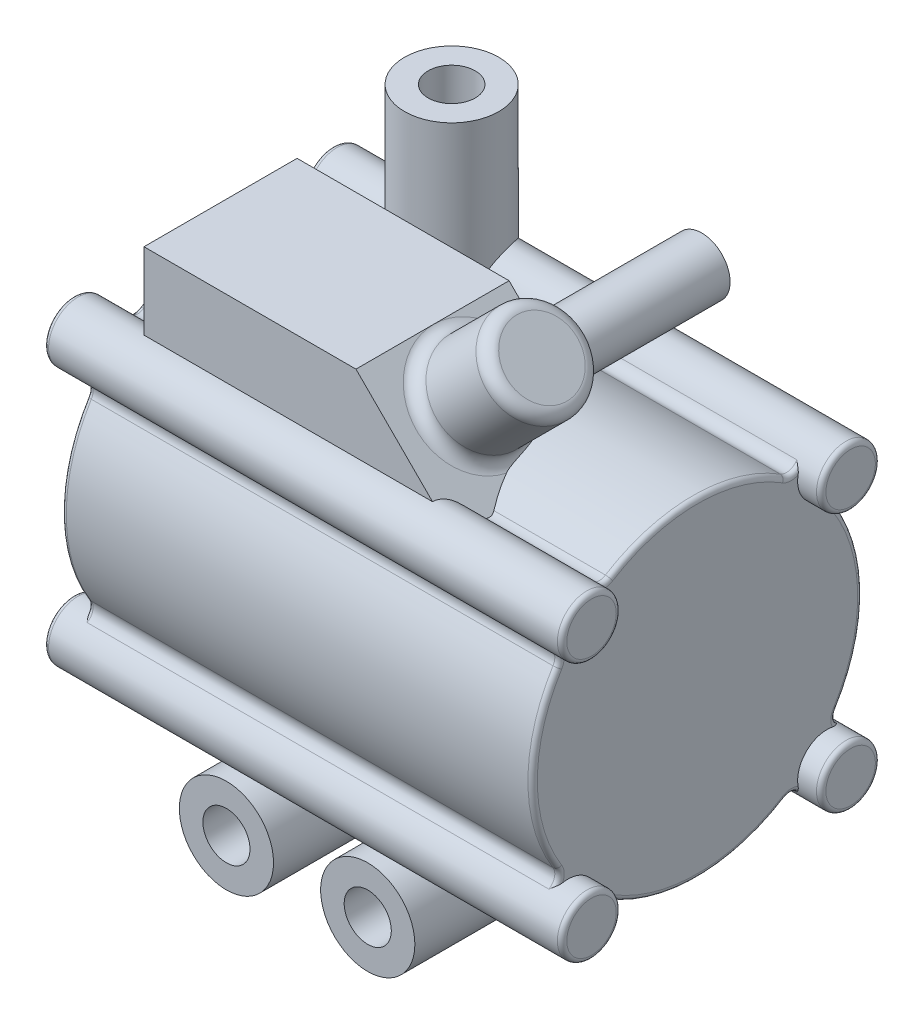
SolidWorks part; units mm, degrees
material "1060 Alloy"
ref_plane "Front Plane" through (0, 0, 0) normal (0, 0, 1) x (1, 0, 0)
ref_plane "Top Plane" through (0, 0, 0) normal (0, 1, 0) x (1, 0, 0)
ref_plane "Right Plane" through (0, 0, 0) normal (1, 0, 0) x (0, 0, -1)
sketch "Sketch1" plane through (0, 0, 0) normal (1, 0, 0) x (0, 0, -1)
  line L1 (27.5, 27.5) -> (-27.5, 27.5) construction
  line L2 (27.5, 27.5) -> (27.5, -27.5) construction
  line L3 (27.5, -27.5) -> (-27.5, -27.5) construction
  line L4 (-27.5, 27.5) -> (-27.5, -27.5) construction
  arc A0 (18.553, 29.678) -> (-18.553, 29.678) centre (0, 0) ccw
  arc A1 (-22.0559, 30.5699) -> (-30.5699, 22.0559) centre (-27.5, 27.5) ccw
  arc A2 (30.5699, 22.0559) -> (22.0559, 30.5699) centre (27.5, 27.5) ccw
  arc A3 (-30.5699, -22.0559) -> (-22.0559, -30.5699) centre (-27.5, -27.5) ccw
  arc A4 (22.0559, -30.5699) -> (30.5699, -22.0559) centre (27.5, -27.5) ccw
  arc A5 (-29.678, 18.553) -> (-29.678, -18.553) centre (0, 0) ccw
  arc A6 (-18.553, -29.678) -> (18.553, -29.678) centre (0, 0) ccw
  arc A7 (29.678, -18.553) -> (29.678, 18.553) centre (0, 0) ccw
  arc A8 (29.678, 18.553) -> (30.5699, 22.0559) centre (31.7979, 19.8783) cw
  arc A9 (30.5699, -22.0559) -> (29.678, -18.553) centre (31.7979, -19.8783) cw
  arc A10 (18.553, -29.678) -> (22.0559, -30.5699) centre (19.8783, -31.7979) cw
  arc A11 (-18.553, -29.678) -> (-22.0559, -30.5699) centre (-19.8783, -31.7979) ccw
  arc A12 (-29.678, -18.553) -> (-30.5699, -22.0559) centre (-31.7979, -19.8783) cw
  arc A13 (-30.5699, 22.0559) -> (-29.678, 18.553) centre (-31.7979, 19.8783) cw
  arc A14 (-22.0559, 30.5699) -> (-18.553, 29.678) centre (-19.8783, 31.7979) ccw
  arc A15 (18.553, 29.678) -> (22.0559, 30.5699) centre (19.8783, 31.7979) ccw
  point P9 (0, 27.5)
  point P15 (27.5, 0)
  point P23 (27.8051, -21.2574)
  point P32 (-27.8051, 21.2574)
  dimension "D1" = 70
  dimension "D2" = 12.5
  dimension "D4" = 2.5
  dimension "D3" = 55
extrude "Boss-Extrude1" add sketch "Sketch1" against normal blind 50 and the other way blind 50
sketch "Sketch2" plane through (0, 0, 0) normal (1, 0, 0) x (0, 0, -1)
  circle A0 centre (-27.5, 27.5) radius 6.25
  circle A1 centre (27.5, 27.5) radius 6.25
  circle A2 centre (27.5, -27.5) radius 6.25
  circle A3 centre (-27.5, -27.5) radius 6.25
extrude "Boss-Extrude2" add sketch "Sketch2" along normal blind 55 and the other way blind 55
fillet "Fillet1" radius 1 8 edges at (-55, -27.5, 21.25) (-55, -27.5, -33.75) (-55, 27.5, 21.25) (-55, 27.5, -33.75) (55, -27.5, 21.25) (55, -27.5, -33.75) (55, 27.5, -33.75) (55, 27.5, 21.25)
fillet "Fillet2" radius 1 24 edges at (50, -20.4951, -29.3752) (50, 20.4951, -29.3752) (50, -29.3752, 20.4951) (50, -29.3752, -20.4951) (50, 20.4951, 29.3752) (50, -20.4951, 29.3752) (50, 29.3752, -20.4951) (50, 29.3752, 20.4951) (-50, -29.3752, 20.4951) (-50, -29.3752, -20.4951) (-50, -20.4951, -29.3752) (-50, 20.4951, -29.3752) (-50, 29.3752, -20.4951) (-50, 29.3752, 20.4951) (-50, 20.4951, 29.3752) (-50, -20.4951, 29.3752) (50, 0, -35) (50, -35, 0) (50, 0, 35) (50, 35, 0) (-50, -35, 0) (-50, 0, -35) (-50, 35, 0) (-50, 0, 35)
sketch "Sketch3" plane through (0, 0, 0) normal (0, 0, 1) x (1, 0, 0)
  circle A0 centre (15, -42) radius 5
  circle A1 centre (-15, -42) radius 5
  circle A2 centre (15, -42) radius 10
  circle A3 centre (-15, -42) radius 10
  dimension "D3" = 20
  dimension "D4" = 10
  dimension "D1" = 15
  dimension "D2" = 15
  dimension "D5" = 42
extrude "Boss-Extrude3" add sketch "Sketch3" along normal blind 35 and the other way blind 35
sketch "Sketch4" plane through (0, 0, 0) normal (0, 1, 0) x (1, 0, 0)
  circle A0 centre (-27.1824, 25) radius 10
  circle A1 centre (-27.1824, 25) radius 5
  dimension "D2" = 10
  dimension "D3" = 20
  dimension "D1" = 25
extrude "Boss-Extrude5" add sketch "Sketch4" along normal blind 60
sketch "Sketch7" plane through (0, 0, 0) normal (0, 0, 1) x (1, 0, 0)
  line L0 (-40, 25) -> (-40, 50)
  line L1 (-40, 50) -> (5, 50)
  line L2 (5, 50) -> (30, 25)
  line L3 (30, 25) -> (-40, 25)
  dimension "D1" = 45
  dimension "D2" = 25
  dimension "D3" = 25
  dimension "D4" = 70
  dimension "D5" = 40
extrude "Boss-Extrude6" add sketch "Sketch7" along normal blind 27.5 and the other way blind 5
sketch "Sketch8" plane through (27.5, 27.5, 0) normal (0.7071, 0.7071, 0) x (0, 0, -1)
  line L0 (5, 31.8198) -> (-27.5, 31.8198) construction
  line L1 (5, 10.0989) -> (5, 31.8198) construction
  circle A0 centre (-11, 19.3198) radius 10
  dimension "D1" = 20
  dimension "D2" = 12.5
  dimension "D3" = 16
extrude "Boss-Extrude7" add sketch "Sketch8" along normal blind 20
sketch "Sketch9" plane through (0, 0, 0) normal (0, 0, 1) x (1, 0, 0)
  line L0 (20.9099, 62.3744) -> (6.7678, 48.2322) construction
  line L1 (35.052, 48.2322) -> (20.9099, 62.3744) construction
  circle A0 centre (20.9099, 48.2322) radius 6
  circle A1 centre (20.9099, 48.2322) radius 4
  dimension "D1" = 10
  dimension "D2" = 10
  dimension "D3" = 12
  dimension "D4" = 8
extrude "Boss-Extrude8" add sketch "Sketch9" along normal blind 10 and the other way blind 30
fillet "Fillet3" radius 2.5 2 edges at (6.7678, 48.2322, 11) (20.9099, 62.3744, 11)
sketch "Sketch10" plane through (-50, 0, 0) normal (-1, 0, 0) x (0, 0, 1)
  circle A0 centre (0, 0) radius 7.5
  dimension "D1" = 15
extrude "Cut-Extrude1" cut sketch "Sketch10" against normal blind 20
sketch "Sketch11" plane through (-50, 0, 0) normal (-1, 0, 0) x (0, 0, 1)
  circle A0 centre (0, 0) radius 7.5
  circle A1 centre (0, 0) radius 10
  dimension "D1" = 15
  dimension "D2" = 20
extrude "Boss-Extrude9" add sketch "Sketch11" along normal blind 7.5
